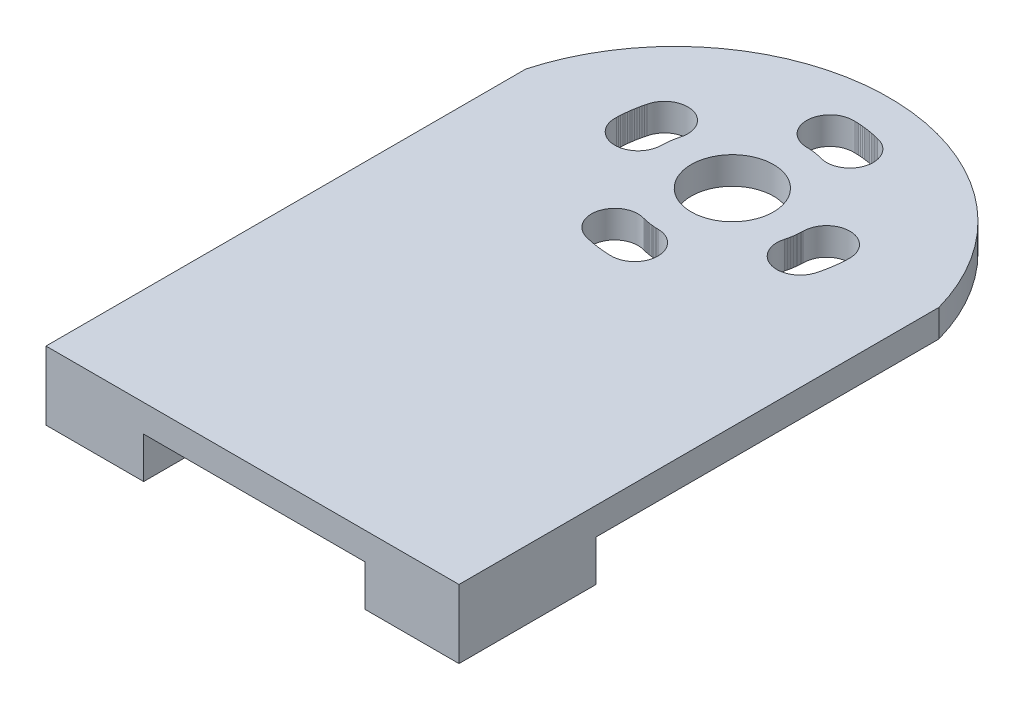
SolidWorks part; units mm, degrees
ref_plane "Front Plane" through (0, 0, 0) normal (0, 0, 1) x (1, 0, 0)
ref_plane "Top Plane" through (0, 0, 0) normal (0, 1, 0) x (1, 0, 0)
ref_plane "Right Plane" through (0, 0, 0) normal (1, 0, 0) x (0, 0, -1)
sketch "Sketch2" plane through (0, 0, 0) normal (0, 1, 0) x (1, 0, 0)
  line L0 (15.061, 0) -> (15.061, 32)
  line L1 (-12.561, 2.5) -> (12.561, 2.5)
  line L2 (-12.561, 2.5) -> (-12.561, 32)
  line L4 (12.561, 2.5) -> (12.561, 32)
  line L5 (15.061, 32) -> (12.561, 32)
  line L7 (-15.061, 32) -> (-15.061, 0)
  line L8 (-15.061, 0) -> (15.061, 0)
  line L10 (-15.061, 32) -> (-12.561, 32)
  point P4 (0, 2.5)
  point P12 (0, 0)
  dimension "D1" = 2.5
  dimension "D2" = 2.5
  dimension "D3" = 29.5
  dimension "D4" = 25.122
extrude "Boss-Extrude1" add sketch "Sketch2" along normal blind 32.5
sketch "Sketch4" plane through (0, 0, 0) normal (0, -1, 0) x (1, 0, 0)
  line L10 (-7.561, -6) -> (-7.561, 0)
  line L13 (-12.561, -2.5) -> (-12.561, -32) construction
  line L18 (-12.561, -10) -> (-7.561, -6)
  line L23 (12.561, -32) -> (12.561, -2.5) construction
  line L26 (12.561, -10) -> (7.561, -6)
  line L33 (-15.061, -32) -> (-15.061, 0) construction
  line L36 (15.061, 0) -> (15.061, -32) construction
  line L38 (-7.561, 0) -> (-15.061, 0)
  line L39 (7.561, -6) -> (7.561, 0)
  line L40 (7.561, 0) -> (15.061, 0)
  line L41 (-15.061, 0) -> (-15.061, -32)
  line L42 (-15.061, -32) -> (-12.561, -32)
  line L43 (-12.561, -32) -> (-15.061, -32) construction
  line L44 (-12.561, -32) -> (-12.561, -10)
  line L45 (12.561, -10) -> (12.561, -32)
  line L46 (12.561, -32) -> (15.061, -32)
  line L47 (15.061, -32) -> (15.061, 0)
  circle A2 centre (-10.2499, -4.95) radius 1.05
  circle A5 centre (10.2499, -4.95) radius 1.05
  dimension "D4" = 6
  dimension "D5" = 2.1
  dimension "D1" = 7.5
  dimension "D2" = 7.5
  dimension "D3" = 10
extrude "Boss-Extrude2" add sketch "Sketch4" along normal blind 2.5
sketch "Sketch5" plane through (0, 32.5, 0) normal (0, 1, 0) x (1, 0, 0)
  line L0 (-15.061, 32) -> (-10.2499, 32)
  line L9 (-10.2499, 32) -> (-6.25, 26)
  line L13 (-15.061, 0) -> (15.061, 0) construction
  line L14 (15.061, 0) -> (-15.061, 0)
  line L15 (-15.061, 0) -> (-15.061, 32)
  line L20 (15.061, 0) -> (15.061, 32)
  line L21 (-6.25, 26) -> (6.25, 26)
  line L22 (6.25, 26) -> (10.2499, 32)
  line L23 (10.2499, 32) -> (15.061, 32)
  circle A0 centre (-10.2499, 4.95) radius 1.05 construction
  circle A1 centre (-10.2499, 8.7) radius 1.05
  circle A2 centre (10.2499, 8.7) radius 1.05
  point P6 (0, 26)
  dimension "D4" = 0
  dimension "D1" = 8.7
  dimension "D2" = 12.5
  dimension "D3" = 20.4998
  dimension "D5" = 6
extrude "Boss-Extrude3" add sketch "Sketch5" along normal blind 3
sketch "Sketch6" plane through (-15.061, 0, 0) normal (-1, 0, 0) x (0, 0, 1)
  line L1 (-32, -2.5) -> (-32, 29.6998)
  line L5 (-32, 35.5) -> (-32, -2.5) construction
  line L7 (0, 35.5) -> (0, -2.5) construction
  line L8 (-12.5, -2.5) -> (-12.5, 35.5)
  line L9 (-32, 35.5) -> (0, 35.5) construction
  line L10 (-12.5, 35.5) -> (-32, 35.5)
  line L11 (-32, 35.5) -> (-32, 29.6998)
  line L12 (0, -2.5) -> (-32, -2.5) construction
  line L13 (-32, -2.5) -> (-12.5, -2.5)
  point P2 (-32.1122, -2.5)
  dimension "D2" = 12.5
extrude "Cut-Extrude1" cut sketch "Sketch6" against normal through all
ref_plane "Plane1" through (0, 16.5, 0) normal (0, -1, 0) x (-1, 0, 0)
sketch "Sketch13" plane through (0, 0, 0) normal (0, 0, 1) x (1, 0, 0)
  line L1 (-15.061, 35.5) -> (15.061, 35.5)
  line L2 (-15.061, 35.5) -> (-15.061, -2.5)
  line L3 (-15.061, -2.5) -> (15.061, -2.5)
  line L4 (15.061, 35.5) -> (15.061, -2.5)
extrude "Boss-Extrude7" add sketch "Sketch13" along normal blind 2.5
sketch "Sketch14" plane through (0, 0, 2.5) normal (0, 0, 1) x (1, 0, 0)
  line L0 (15.061, 35.5) -> (-15.061, 35.5) construction
  line L1 (-7.9361, 35.5) -> (8.206, 35.5)
  line L2 (-7.9361, 35.5) -> (-7.9361, 29.3758)
  line L3 (-7.9361, 29.3758) -> (8.206, 29.3758)
  line L4 (8.206, 35.5) -> (8.206, 29.3758)
extrude "Cut-Extrude2" cut sketch "Sketch14" against normal through all both and the other way through all
sketch "Sketch15" plane through (0, 0, -12.5) normal (0, 0, -1) x (-1, 0, 0)
  line L0 (15.061, -2.5) -> (15.061, 35.5) construction
  line L1 (-15.061, 35.5) -> (15.061, 35.5)
  line L2 (-15.061, 35.5) -> (-15.061, 37.5)
  line L3 (-15.061, 37.5) -> (15.061, 37.5)
  line L4 (15.061, 35.5) -> (15.061, 37.5)
  dimension "D1" = 2
extrude "Boss-Extrude8" add sketch "Sketch15" against normal up to surface (15 mm away) and the other way blind 40 up to face at (0.0675, 24.469, 2.5)
sketch "Sketch16" plane through (0, 37.5, 0) normal (0, 1, 0) x (1, 0, 0)
  line L0 (-15.061, -2.5) -> (15.061, -2.5) construction
  circle A0 centre (0, 37.5) radius 3
  point P2 (0, 0)
  dimension "D1" = 6
  dimension "D2" = 40
extrude "Cut-Extrude3" cut sketch "Sketch16" against normal through all both and the other way through all
sketch "Sketch17" plane through (0, 37.5, 0) normal (0, 1, 0) x (1, 0, 0)
  circle A0 centre (1.8162, 44.2603) radius 1.7
  circle A2 centre (0, 37.5) radius 3 construction
  dimension "D1" = 3.4
  dimension "D2" = 1.8162
  dimension "D3" = 6.7603
extrude "Cut-Extrude4" cut sketch "Sketch17" against normal through all both and the other way through all
ref_axis "Axis1" through (0, 35.5, -37.5) along (0, 1, 0)
pattern_circular "CirPattern1" count 15 every 1 about axis through (0, 35.5, -37.5) along (0, 1, 0) of "Cut-Extrude4"
pattern_circular "CirPattern2" count 4 over 360 about axis through (0, 35.5, -37.5) along (0, 1, 0) of "CirPattern1"
sketch "Sketch19" plane through (0, 0, -12.5) normal (0, 0, -1) x (-1, 0, 0)
  line L1 (-15.061, 8.7299) -> (15.061, 8.7299)
  line L2 (-15.061, 8.7299) -> (-15.061, -7.1783)
  line L3 (-15.061, -7.1783) -> (15.061, -7.1783)
  line L4 (15.061, 8.7299) -> (15.061, -7.1783)
  point P6 (15.061, 0.8705)
  point P9 (15.061, -7.1783)
extrude "Cut-Extrude5" cut sketch "Sketch19" against normal through all both and the other way through all
sketch "Sketch20" plane through (0, 8.7299, 0) normal (0, -1, 0) x (1, 0, 0)
  line L1 (-15.061, 2.5) -> (16.4822, 2.5)
  line L2 (-15.061, 2.5) -> (-15.061, -2.5)
  line L3 (-15.061, -2.5) -> (16.4822, -2.5)
  line L4 (16.4822, 2.5) -> (16.4822, -2.5)
  point P4 (16.4822, -2.5)
extrude "Cut-Extrude6" cut sketch "Sketch20" against normal through all both and the other way through all
sketch "Sketch22" plane through (0, 0, -12.5) normal (0, 0, -1) x (-1, 0, 0)
  line L0 (-15.061, 8.7299) -> (-15.061, 35.5) construction
  line L1 (-15.061, 32.5) -> (15.061, 32.5)
  line L2 (-15.061, 32.5) -> (-15.061, 8.7299)
  line L3 (-15.061, 8.7299) -> (15.061, 8.7299)
  line L4 (15.061, 32.5) -> (15.061, 8.7299)
extrude "Cut-Extrude7" cut sketch "Sketch22" against normal through all both and the other way through all
sketch "Sketch23" plane through (0, 37.5, 0) normal (0, 1, 0) x (1, 0, 0)
  line L9 (-15.061, 52.5) -> (-15.061, 2.5) construction
  line L10 (15.061, 52.5) -> (15.061, 2.5) construction
  line L11 (-15.061, 37.5) -> (-15.061, 55.7627)
  line L12 (-15.061, 55.7627) -> (15.061, 55.1353)
  line L13 (15.061, 55.1353) -> (15.061, 37.5)
  arc A1 (-15.061, 37.5) -> (15.061, 37.5) centre (0, 33.3084) cw
extrude "Cut-Extrude8" cut sketch "Sketch23" against normal through all both and the other way through all
